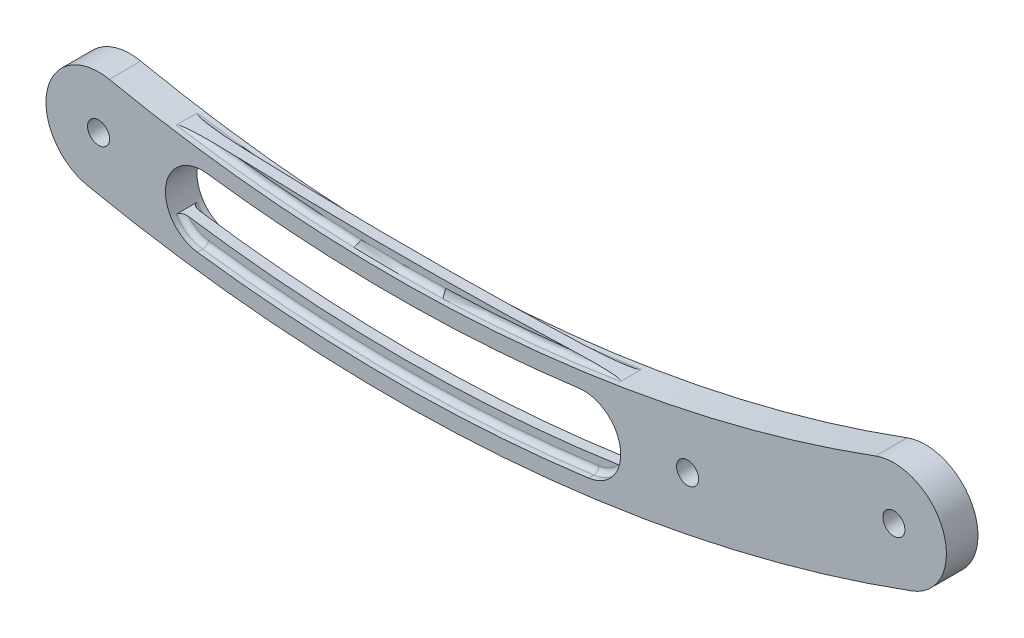
SolidWorks part; units mm, degrees
material "PLA"
ref_plane "Alzado" through (0, 0, 0) normal (0, 0, 1) x (1, 0, 0)
ref_plane "Planta" through (0, 0, 0) normal (0, 1, 0) x (1, 0, 0)
ref_plane "Vista lateral" through (0, 0, 0) normal (1, 0, 0) x (0, 0, -1)
sketch "Croquis1" plane through (0, 0, 0) normal (0, 0, 1) x (1, 0, 0)
  line L0 (-112, 0) -> (0, 0) construction
  line L1 (0, 0) -> (39.2195, 11.246) construction
  arc A0 (-112, 0) -> (39.2195, 11.246) centre (-56, 269.3055) ccw construction
  arc A1 (-114.0359, -9.7906) -> (42.6812, 1.8643) centre (-56, 269.3055) ccw
  arc A2 (-109.9641, 9.7906) -> (35.7578, 20.6277) centre (-56, 269.3055) ccw
  arc A3 (-109.9641, 9.7906) -> (-114.0359, -9.7906) centre (-112, 0) ccw
  arc A4 (42.6812, 1.8643) -> (35.7578, 20.6277) centre (39.2195, 11.246) ccw
  circle A5 centre (0, 0) radius 2.1
  circle A6 centre (39.2195, 11.246) radius 2.1
  circle A7 centre (-112, 0) radius 2.1
  arc A8 (-92.2838, -3.3572) -> (-19.7162, -3.3572) centre (-56, 269.3055) ccw construction
  arc A9 (-93.2071, -10.296) -> (-18.7929, -10.296) centre (-56, 269.3055) ccw
  arc A10 (-91.3604, 3.5816) -> (-20.6396, 3.5816) centre (-56, 269.3055) ccw
  arc A11 (-91.3604, 3.5816) -> (-93.2071, -10.296) centre (-92.2838, -3.3572) ccw
  arc A12 (-18.7929, -10.296) -> (-20.6396, 3.5816) centre (-19.7162, -3.3572) ccw
  point P4 (-35.6, -5.0033)
  point P18 (-56, -5.7608)
  dimension "D4" = 20
  dimension "D5" = 4.2
  dimension "D6" = 4.2
  dimension "D7" = 4.2
  dimension "D9" = 20
  dimension "D10" = 3
  dimension "D1" = 16
  dimension "D2" = 40.8
  dimension "D3" = 112
  dimension "D8" = 20
extrude "Saliente-Extruir1" add sketch "Croquis1" along normal blind 6
ref_plane "Plano6" through (0, 0, 3) normal (0, 0, 1) x (1, 0, 0)
sketch "Croquis3" plane through (0, 0, 3) normal (0, 0, 1) x (1, 0, 0)
  arc A0 (-99.2226, -2.4338) -> (-12.7774, -2.4338) centre (-56, 269.3055) ccw construction
  arc A1 (-91.3604, 3.5816) -> (-93.2071, -10.296) centre (-92.2838, -3.3572) ccw construction
  arc A2 (-18.7929, -10.296) -> (-20.6396, 3.5816) centre (-19.7162, -3.3572) ccw construction
  arc A3 (-98.2286, -7.053) -> (-93.2071, -10.296) centre (-92.2838, -3.3572) ccw
  arc A4 (-93.2071, -10.296) -> (-18.7929, -10.296) centre (-56, 269.3055) ccw
  arc A5 (-93.2071, -10.296) -> (-18.7929, -10.296) centre (-56, 269.3055) ccw construction
  arc A6 (-98.2286, -7.053) -> (-13.7714, -7.053) centre (-56, 269.3055) ccw
  arc A7 (-13.7714, -7.053) -> (-18.7929, -10.296) centre (-19.7162, -3.3572) cw
  arc A8 (-98.2286, 7.6246) -> (-13.7714, 7.6246) centre (-56, 842.3166) ccw
  arc A9 (-98.2286, 7.6246) -> (-13.7714, 7.6246) centre (-56, 269.3055) ccw
  arc A10 (-109.9641, 9.7906) -> (35.7578, 20.6277) centre (-56, 269.3055) ccw construction
  dimension "D1" = 2.5
extrude "Saliente-Extruir3" add sketch "Croquis3" along normal mid plane 2
fillet "Redondeo2" radius 1 8 edges at (-96.0814, -9.2375, 2) (-15.9186, -9.2375, 2) (-96.0814, -9.2375, 4) (-15.9186, -9.2375, 4) (-56, -12.7608, 2) (-56, -12.7608, 4) (-56, 4.2392, 2) (-56, 4.2392, 4)
